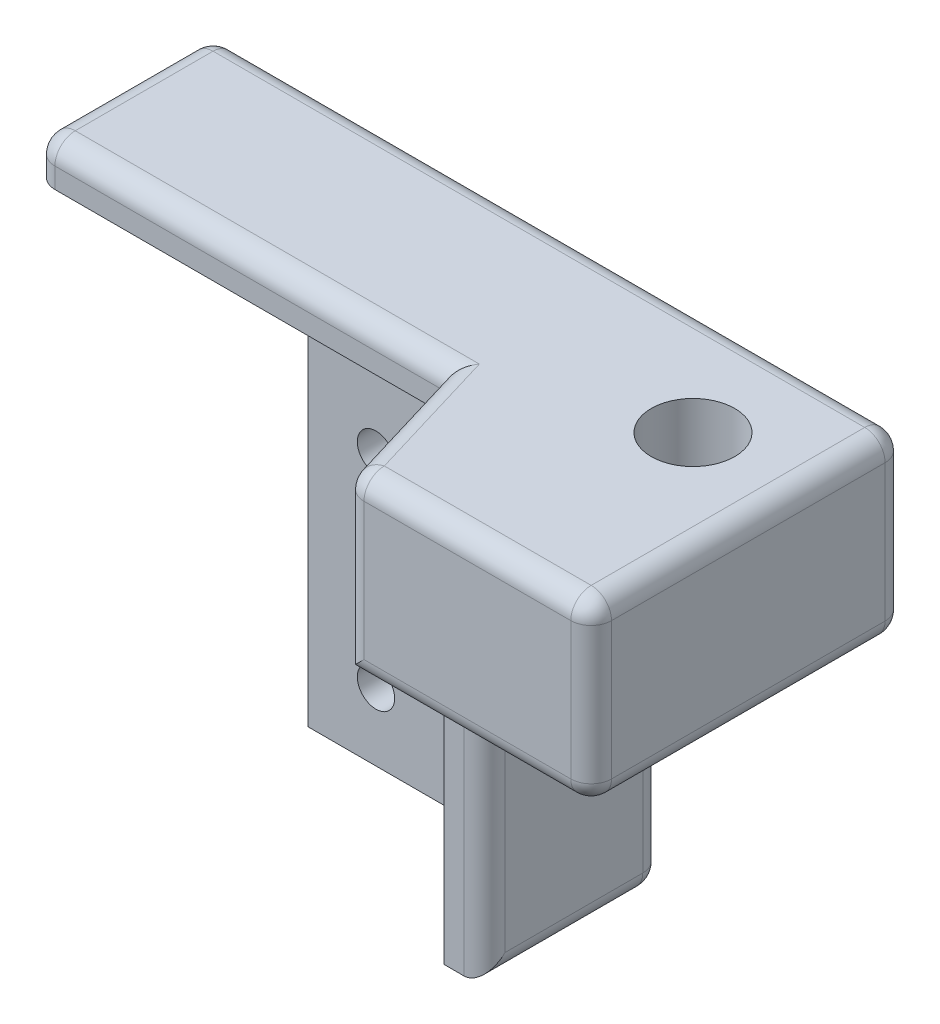
SolidWorks part; units mm, degrees
ref_plane "Front Plane" through (0, 0, 0) normal (0, 0, 1) x (1, 0, 0)
ref_plane "Top Plane" through (0, 0, 0) normal (0, 1, 0) x (1, 0, 0)
ref_plane "Right Plane" through (0, 0, 0) normal (1, 0, 0) x (0, 0, -1)
sketch "Sketch1" plane through (0, 0, 0) normal (0, 1, 0) x (1, 0, 0)
  line L0 (60, 26.3) -> (60, 0) construction
  line L1 (0, 0) -> (102, 0)
  line L2 (0, 0) -> (0, 26.3)
  line L3 (0, 26.3) -> (102, 26.3)
  line L4 (102, 0) -> (102, 26.3)
  circle A0 centre (87, 10) radius 6.15
  dimension "D4" = 12.3
  dimension "D1" = 26.3
  dimension "D2" = 60
  dimension "D3" = 15
  dimension "D5" = 27
  dimension "D6" = 10
extrude "base" add sketch "Sketch1" along normal blind 20.2
sketch "Sketch2" plane through (0, 20.2, 0) normal (0, 1, 0) x (1, 0, 0)
  line L0 (0, 26.3) -> (0, 0) construction
  line L1 (0, 0) -> (60.3, 0)
  line L2 (0, 0) -> (0, 20.3)
  line L3 (0, 20.3) -> (60.3, 20.3)
  line L4 (60.3, 0) -> (60.3, 20.3)
  circle A0 centre (87, 10) radius 6.15 construction
  dimension "D1" = 20.3
  dimension "D2" = 26.7
extrude "backside surface 1" cut sketch "Sketch2" against normal up to next and the other way through all
sketch "Sketch4" plane through (0, 0, 0) normal (0, 1, 0) x (1, 0, 0)
  line L0 (60.3, 0) -> (60.3, 20.3) construction
  line L1 (60.3, 26.3) -> (66.3, 26.3)
  line L2 (60.3, 26.3) -> (60.3, 0)
  line L3 (60.3, 0) -> (66.3, 0)
  line L4 (66.3, 26.3) -> (66.3, 0)
  line L5 (60.3, 0) -> (102, 0) construction
  line L6 (102, 26.3) -> (0, 26.3) construction
  dimension "D1" = 6
extrude "leg" add sketch "Sketch4" against normal blind 50
sketch "Sketch5" plane through (0, 0, 0) normal (-1, 0, 0) x (0, 0, 1)
  line L0 (-26.3, 20.2) -> (-26.3, 26.2)
  line L1 (-26.3, 26.2) -> (0, 26.2)
  line L2 (0, 26.2) -> (0, 20.2)
  line L7 (0, 20.2) -> (-26.3, 20.2)
  line L8 (-26.3, 0) -> (-26.3, -50) construction
  dimension "D2" = 6
extrude "roof" add sketch "Sketch5" against normal up to surface (102 mm away) up to face at (102, 10.1, -13.15)
sketch "Sketch6" plane through (0, 0, 0) normal (0, -1, 0) x (1, 0, 0)
  circle A0 centre (87, -10) radius 6.15
  circle A1 centre (87, -10) radius 6.15 construction
extrude "hole for linear rod" cut sketch "Sketch6" against normal up to surface (26.2 mm away) up to face at (51, 26.2, -13.15)
sketch "Sketch9" plane through (0, 26.2, 0) normal (0, 1, 0) x (1, 0, 0)
  line L1 (66.3, -20) -> (102, -20)
  line L2 (66.3, -20) -> (66.3, 0)
  line L3 (66.3, 0) -> (102, 0)
  line L4 (102, -20) -> (102, 0)
  dimension "D1" = 20
extrude "Boss-Extrude5" add sketch "Sketch9" against normal up to surface (26.2 mm away) up to face at (87, 0, -3.85)
sketch "Sketch7" plane through (0, 0, -26.3) normal (0, 0, 1) x (1, 0, 0)
  line L1 (60.3, 0) -> (20, 0)
  line L2 (60.3, 0) -> (60.3, -50)
  line L3 (60.3, -50) -> (20, -50)
  line L4 (20, 0) -> (20, -50)
  dimension "D1" = 40.3
extrude "backside surface 2" add sketch "Sketch7" along normal up to surface (6 mm away) up to face at (30.15, 10.1, -20.3)
sketch "Sketch3" plane through (0, 0, -26.3) normal (0, 0, 1) x (1, 0, 0)
  line L0 (20, 0) -> (20, -50) construction
  line L1 (40, -50) -> (40, 0) construction
  line L4 (32, 20) -> (32, 0) construction
  line L5 (60.3, -50) -> (66.3, -50) construction
  circle A0 centre (12, 10) radius 2.75
  circle A1 centre (52, 10) radius 2.75
  circle A2 centre (30, -10) radius 2.75
  circle A3 centre (30, -40) radius 2.75
  circle A4 centre (50, -40) radius 2.75
  circle A5 centre (50, -10) radius 2.75
  point P4 (32, 10)
  dimension "D2" = 5.5
  dimension "D1" = 40
  dimension "D3" = 20
  dimension "D4" = 12
  dimension "D5" = 20
  dimension "D6" = 20
  dimension "D7" = 10
  dimension "D8" = 30
extrude "bolt holes" cut sketch "Sketch3" along normal up to next
chamfer "Chamfer1" distance 20 distance2 6 1 edges at (66.3, 13.1, 0)
fillet "Fillet1" radius 3 22 edges at (30.15, 26.2, 0) (63.3, 0, 0) (63.3, 26.2, 10) (43.15, -50, -26.3) (66.3, -50, -13.15) (66.3, -25, -26.3) (66.3, -25, 0) (66.3, 0, -13.15) (84.15, 0, -26.3) (102, 0, -3.15) (51, 26.2, -26.3) (0, 23.2, 0) (0, 26.2, -13.15) (102, 26.2, -3.15) (84.15, 26.2, 20) (84.15, 0, 20) (102, 13.1, 20) (66.3, 13.1, 20) (0, 13.1, -26.3) (102, 13.1, -26.3) (10, 0, -26.3) (20, -25, -26.3)
